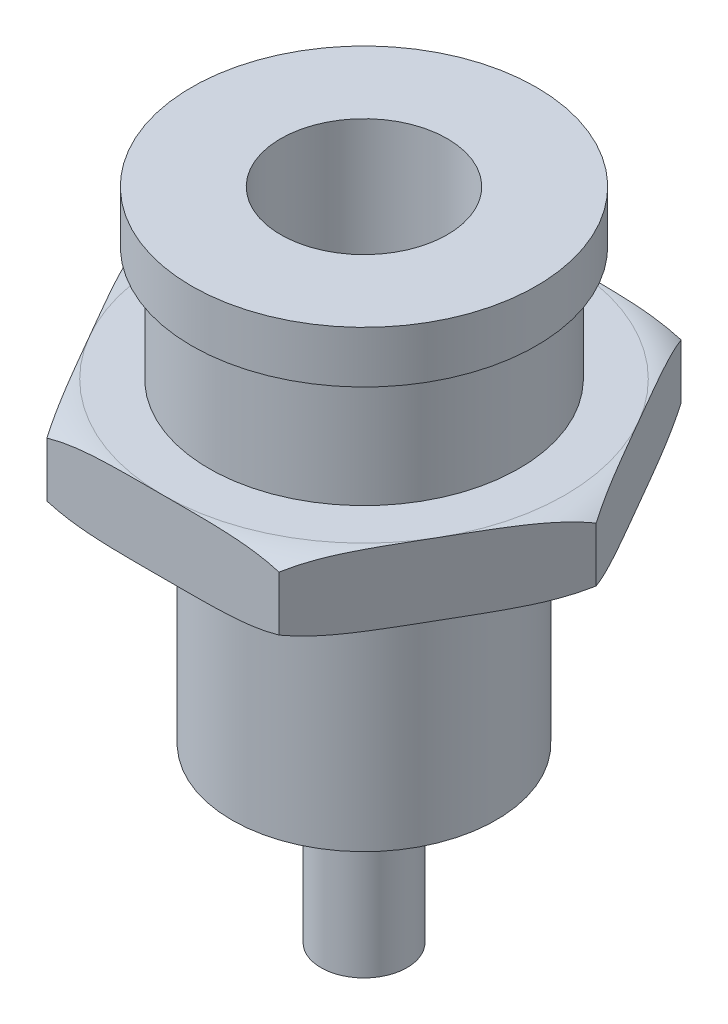
SolidWorks part; units mm, degrees
ref_plane "Front Plane" through (0, 0, 0) normal (0, 0, 1) x (1, 0, 0)
ref_plane "Top Plane" through (0, 0, 0) normal (0, 1, 0) x (1, 0, 0)
ref_plane "Right Plane" through (0, 0, 0) normal (1, 0, 0) x (0, 0, -1)
sketch "Sketch1" plane through (0, 0, 0) normal (0, 0, 1) x (1, 0, 0)
  line L0 (0, 0) -> (0, 12.8)
  line L1 (2.9, 22.8) -> (6, 22.8)
  line L2 (6, 22.8) -> (6, 21)
  line L3 (6, 21) -> (5.4, 21)
  line L4 (5.4, 21) -> (5.4, 16)
  line L5 (5.4, 16) -> (4.6, 16)
  line L6 (4.6, 16) -> (4.6, 6)
  line L7 (4.6, 6) -> (1.5, 6)
  line L8 (1.5, 6) -> (1.5, 0)
  line L9 (1.5, 0) -> (0, 0)
  line L10 (2.9, 22.8) -> (2.9, 12.8)
  line L11 (2.9, 12.8) -> (0, 12.8)
  dimension "D1" = 6
  dimension "D2" = 1.8
  dimension "D3" = 22.8
  dimension "D4" = 5.4
  dimension "D5" = 6.8
  dimension "D6" = 16.8
  dimension "D7" = 4.6
  dimension "D8" = 1.5
  dimension "D9" = 2.9
  dimension "D10" = 10
revolve "Revolve1" add sketch "Sketch1" angle 360 about L0
sketch "Sketch2" plane through (0, 21, 0) normal (0, -1, 0) x (1, 0, 0)
  line L1 (8.0829, 0) -> (4.0415, 7)
  line L2 (4.0415, 7) -> (-4.0415, 7)
  line L3 (-4.0415, 7) -> (-8.0829, 0)
  line L4 (-8.0829, 0) -> (-4.0415, -7)
  line L5 (-4.0415, -7) -> (4.0415, -7)
  line L6 (4.0415, -7) -> (8.0829, 0)
  circle A0 centre (0, 0) radius 7 construction
  point P11 (0, 0)
  dimension "D1" = 14
extrude "Boss-Extrude1" add sketch "Sketch2" along normal blind 2.5 from offset 4
sketch "Sketch3" plane through (0, 0, 0) normal (0, 0, 1) x (1, 0, 0)
  line L0 (-8.0829, 14.5) -> (-8.0829, 17) construction
  line L1 (-4.0415, 17) -> (-8.0829, 17) construction
  line L2 (-4.0415, 14.5) -> (-8.0829, 14.5) construction
  line L3 (-8.0829, 16.7) -> (-8.0829, 17)
  line L4 (-8.0829, 17) -> (-7, 17)
  line L5 (-8.0829, 14.8) -> (-8.0829, 14.5)
  line L6 (-8.0829, 14.5) -> (-7, 14.5)
  line L7 (4.0415, 17) -> (-4.0415, 17) construction
  line L8 (0, 14.5) -> (0, 17) construction
  line L9 (4.0415, 14.5) -> (-4.0415, 14.5) construction
  arc A0 (-8.0829, 16.7) -> (-7, 17) centre (-7, 14.8955) cw
  arc A1 (-8.0829, 14.8) -> (-7, 14.5) centre (-7, 16.6045) ccw
  point P19 (0, 17)
  dimension "D1" = 7
  dimension "D2" = 0.3
revolve "Cut-Revolve1" cut sketch "Sketch3" angle 360 about L8
